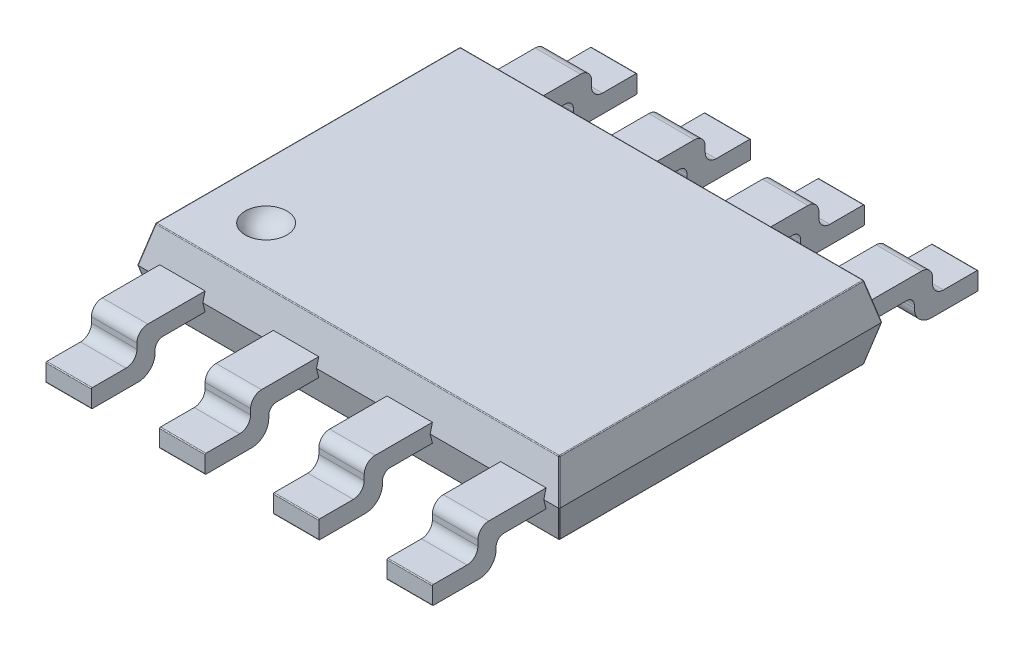
SolidWorks part; units mm, degrees
ref_plane "Front Plane" through (0, 0, 0) normal (0, 0, 1) x (1, 0, 0)
ref_plane "Top Plane" through (0, 0, 0) normal (0, 1, 0) x (1, 0, 0)
ref_plane "Right Plane" through (0, 0, 0) normal (1, 0, 0) x (0, 0, -1)
sketch "Sketch1" plane through (0, 0, 0) normal (0, 1, 0) x (1, 0, 0)
  line L1 (-2.32, -1.775) -> (2.32, -1.775)
  line L2 (-2.32, -1.775) -> (-2.32, 1.775)
  line L3 (-2.32, 1.775) -> (2.32, 1.775)
  line L4 (2.32, -1.775) -> (2.32, 1.775)
  line L5 (-2.32, -1.775) -> (2.32, 1.775) construction
  line L6 (-2.32, 1.775) -> (2.32, -1.775) construction
  point P0 (0, 0)
  dimension "D1" = 3.55
  dimension "D2" = 4.64
extrude "Boss-Extrude1" add sketch "Sketch1" along normal mid plane 0.8
sketch "Sketch2" plane through (2.32, 0, 0) normal (1, 0, 0) x (0, 0, -1)
  line L0 (-1.775, 0) -> (1.775, 0) construction
  line L1 (1.775, 0.4) -> (1.775, -0.4) construction
  line L2 (-1.775, -0.4) -> (-1.775, 0.4)
  line L3 (-1.775, 0.4) -> (-1.675, 0.4)
  line L4 (-1.775, 0.4) -> (1.775, 0.4) construction
  line L5 (-1.675, 0.4) -> (-1.775, 0)
  line L6 (0, -0.4) -> (0, 0.4) construction
  line L7 (-1.675, -0.4) -> (-1.775, 0)
  line L8 (-1.775, -0.4) -> (-1.675, -0.4)
  line L9 (1.775, -0.4) -> (1.675, -0.4)
  line L10 (1.675, -0.4) -> (1.775, 0)
  line L11 (1.675, 0.4) -> (1.775, 0)
  line L12 (1.775, 0.4) -> (1.675, 0.4)
  line L13 (1.775, -0.4) -> (1.775, 0.4)
  point P6 (0, 0)
  point P15 (0, 0)
  line M4 (-1.775, -0.4) -> (1.775, -0.4)
  line M5 (1.775, -0.4) -> (1.775, 0.4)
  line M6 (1.775, 0.4) -> (-1.775, 0.4)
  line M7 (-1.775, 0.4) -> (-1.775, -0.4)
  dimension "D1" = 0.1
extrude "Cut-Extrude1" cut sketch "Sketch2" against normal through all contours L5 M6 M7 | L7 L2 M4 | L11 M6 M5 | L10 M4 M5 region at (2.32, -0.2667, 1.7417) region at (2.32, 0.2667, 1.7417) region at (2.32, -0.2667, -1.7417) region at (2.32, 0.2667, -1.7417)
sketch "Sketch3" plane through (0, 0, 0) normal (0, 0, 1) x (1, 0, 0)
  line L0 (-2.32, 0) -> (-2.22, 0.4)
  line L1 (-2.32, 0.4) -> (2.32, 0.4) construction
  line L2 (-2.22, 0.4) -> (-2.32, 0.4)
  line L3 (-2.32, 0.4) -> (-2.32, -0.4)
  line L4 (-2.32, 0) -> (2.32, 0) construction
  line L6 (0, -0.4) -> (0, 0.4) construction
  line L7 (-2.22, -0.4) -> (-2.32, -0.4)
  line L8 (-2.32, 0) -> (-2.22, -0.4)
  line L9 (2.32, 0) -> (2.22, -0.4)
  line L10 (2.22, -0.4) -> (2.32, -0.4)
  line L11 (2.32, 0.4) -> (2.32, -0.4)
  line L12 (2.22, 0.4) -> (2.32, 0.4)
  line L13 (2.32, 0) -> (2.22, 0.4)
  point P9 (0, 0)
  point P15 (0, 0)
  dimension "D1" = 0.1
extrude "Cut-Extrude2" cut sketch "Sketch3" against normal through all both and the other way through all contours L2 L3 L0 | L8 L3 L7 | L13 L11 L12 | L11 L9 L10 region at (-2.2867, 0.2667, 0) region at (-2.2867, -0.2667, 0) region at (2.2867, -0.2667, 0) region at (2.2867, 0.2667, 0)
fillet "Fillet1" radius 0.01 16 edges at (0, -0.4, -1.675) (2.27, 0.2, -1.725) (2.27, -0.2, -1.725) (2.22, -0.4, 0) (2.27, -0.2, 1.725) (2.27, 0.2, 1.725) (-2.27, -0.2, -1.725) (-2.27, 0.2, -1.725) (-2.22, -0.4, 0) (0, -0.4, 1.675) (-2.27, -0.2, 1.725) (-2.27, 0.2, 1.725) (0, 0.4, -1.675) (0, 0.4, 1.675) (-2.22, 0.4, 0) (2.22, 0.4, 0)
sketch "Sketch4" plane through (0, 0, 0) normal (1, 0, 0) x (0, 0, -1)
  line L0 (-1.775, 0) -> (-1.8869, 0) construction
  line L1 (-1.75, 0.1) -> (-2.38, 0.1)
  line L2 (-1.775, 0) -> (-1.6769, 0.3924) construction
  line L3 (-2.5, -0.02) -> (-2.5, -0.08)
  line L4 (-2.62, -0.2) -> (-2.99, -0.2)
  line L5 (-3, -0.21) -> (-3, -0.39)
  line L6 (-2.99, -0.4) -> (-2.4862, -0.4)
  line L7 (-2.3, -0.2138) -> (-2.3, -0.1859)
  line L8 (-2.2141, -0.1) -> (-1.75, -0.1)
  line L9 (-1.6769, -0.3924) -> (-1.775, 0) construction
  line L10 (-1.75, -0.1) -> (-1.775, 0)
  line L11 (-1.775, 0) -> (-1.75, 0.1)
  line L12 (1.6672, -0.4) -> (-1.6672, -0.4) construction
  arc A0 (-2.4862, -0.4) -> (-2.3, -0.2138) centre (-2.4862, -0.2138) ccw
  arc A1 (-2.5, -0.08) -> (-2.62, -0.2) centre (-2.62, -0.08) cw
  arc A2 (-2.3, -0.1859) -> (-2.2141, -0.1) centre (-2.2141, -0.1859) cw
  arc A3 (-2.38, 0.1) -> (-2.5, -0.02) centre (-2.38, -0.02) ccw
  arc A4 (-3, -0.39) -> (-2.99, -0.4) centre (-2.99, -0.39) ccw
  arc A5 (-2.99, -0.2) -> (-3, -0.21) centre (-2.99, -0.21) ccw
  point P22 (-2.5, -0.2)
  point P27 (-2.5, 0.1)
  point P32 (-3, -0.2)
  dimension "D6" = 0.12
  dimension "D7" = 0.01
  dimension "D1" = 0.75
  dimension "D2" = 0.5
  dimension "D3" = 0.2
  dimension "D4" = 0.2
  dimension "D5" = 0.2
extrude "Boss-Extrude2" add sketch "Sketch4" against normal mid plane 0.5 from offset 0.6 offset against normal yes
fillet "Fillet2" radius 0.01 26 edges at (-0.85, 0.1, 2.065) (-0.85, 0.0649, 2.4649) (-0.85, -0.05, 2.5) (-0.85, -0.1649, 2.5351) (-0.85, -0.2, 2.805) (-0.85, -0.2029, 2.9971) (-0.85, -0.1, 1.982) (-0.85, -0.1252, 2.2748) (-0.85, -0.1998, 2.3) (-0.85, -0.3455, 2.3545) (-0.85, -0.4, 2.7381) (-0.85, -0.3971, 2.9971) (-0.35, 0.1, 2.065) (-0.35, 0.0649, 2.4649) (-0.35, -0.05, 2.5) (-0.35, -0.1649, 2.5351) (-0.35, -0.2, 2.805) (-0.35, -0.2029, 2.9971) (-0.35, -0.1, 1.982) (-0.35, -0.1252, 2.2748) (-0.35, -0.1998, 2.3) (-0.35, -0.3455, 2.3545) (-0.35, -0.4, 2.7381) (-0.35, -0.3971, 2.9971) (-0.85, -0.3, 3) (-0.35, -0.3, 3)
pattern_linear "LPattern1" count 3 spacing 1.25 along (1, 0, 0) count 2 spacing 1.25 along (-1, 0, 0) of "Boss-Extrude2"
mirror "Mirror1" about plane through (0, 0, 0) normal (0, 0, 1) of "LPattern1"
ref_plane "Plane1" through (0, 0.5, 0) normal (0, 1, 0) x (1, 0, 0)
sketch "Sketch5" plane through (0, 0.5, 0) normal (0, 1, 0) x (1, 0, 0)
  line L0 (-2.2122, 1.6672) -> (-2.2122, -1.6672) construction
  line L1 (-2.2122, -1.6672) -> (2.2122, -1.6672) construction
  line L2 (-1.3622, -1.0672) -> (-1.8622, -1.0672)
  arc A0 (-1.3622, -1.0672) -> (-1.8622, -1.0672) centre (-1.6122, -1.0672) ccw
  dimension "D1" = 0.5
  dimension "D2" = 0.6
  dimension "D3" = 0.6
revolve "Cut-Revolve1" cut sketch "Sketch5" angle 360 about L2
